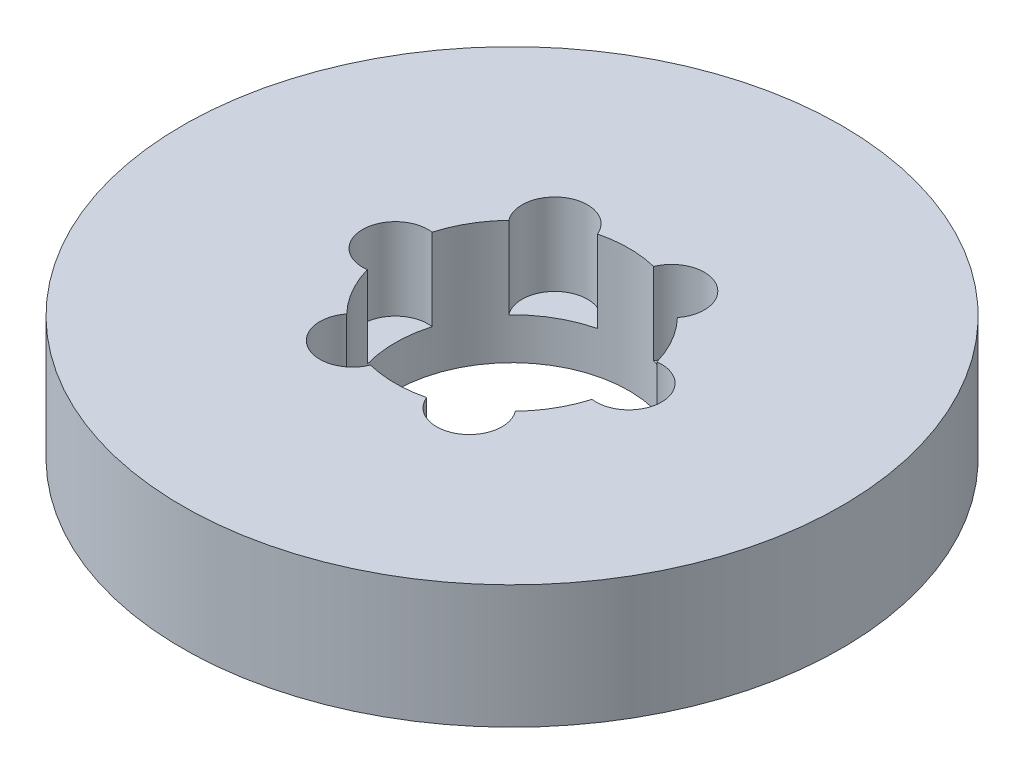
SolidWorks part; units mm, degrees
ref_plane "Front Plane" through (0, 0, 0) normal (0, 0, 1) x (1, 0, 0)
ref_plane "Top Plane" through (0, 0, 0) normal (0, 1, 0) x (1, 0, 0)
ref_plane "Right Plane" through (0, 0, 0) normal (1, 0, 0) x (0, 0, -1)
sketch "Sketch1" plane through (0, 0, 0) normal (0, 1, 0) x (1, 0, 0)
  circle A0 centre (0, 0) radius 77.5
  dimension "FLANGE_OD" = 155
extrude "Boss-Extrude1" add sketch "Sketch1" along normal blind 29
sketch "Sketch2" plane through (0, 0, 0) normal (0, 1, 0) x (1, 0, 0)
  circle A0 centre (0, 0) radius 27.5
  dimension "BORE_D" = 55
extrude "Cut-Extrude1" cut sketch "Sketch2" along normal through all
sketch "Sketch3" plane through (0, 29, 0) normal (0, 1, 0) x (1, 0, 0)
  circle A0 centre (0, 0) radius 27.4543 construction
  circle A1 centre (-27.4543, 0) radius 7.7004
  dimension "BOLT_D" = 15.4009
  dimension "BOLT_PCD" = 54.9086
extrude "Cut-Extrude2" cut sketch "Sketch3" against normal blind 19.238
pattern_circular "CirPattern1" count 6 over 360 about axis through (0, 0, 0) along (0, 1, 0) of "Cut-Extrude2"
